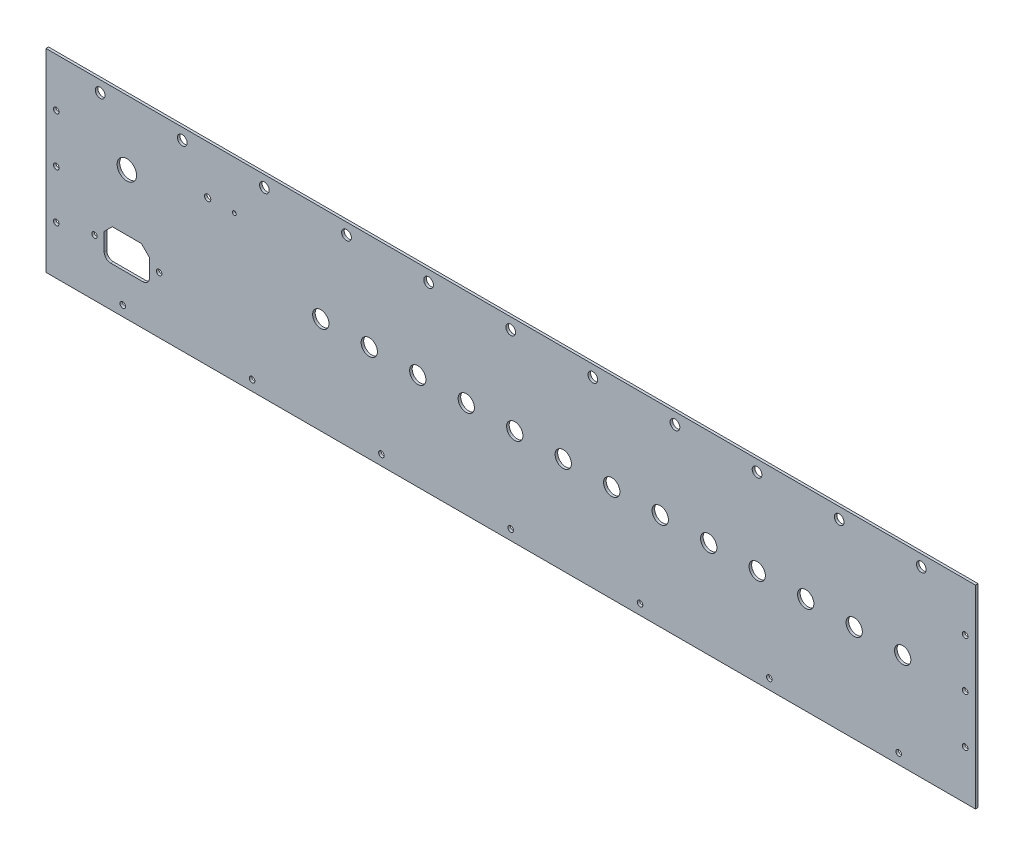
SolidWorks part; units mm, degrees
ref_plane "Front Plane" through (0, 0, 0) normal (0, 0, 1) x (1, 0, 0)
ref_plane "Top Plane" through (0, 0, 0) normal (0, 1, 0) x (1, 0, 0)
ref_plane "Right Plane" through (0, 0, 0) normal (1, 0, 0) x (0, 0, -1)
sketch "Sketch1" plane through (0, 0, 0) normal (0, 0, 1) x (1, 0, 0)
  line L1 (287.5, -60) -> (-287.5, -60)
  line L2 (287.5, -60) -> (287.5, 60)
  line L3 (287.5, 60) -> (-287.5, 60)
  line L4 (-287.5, -60) -> (-287.5, 60)
  line L5 (287.5, -60) -> (-287.5, 60) construction
  line L6 (287.5, 60) -> (-287.5, -60) construction
  point P0 (0, 0)
  dimension "D1" = 120
  dimension "D2" = 575
extrude "Boss-Extrude1" add sketch "Sketch1" along normal blind 1.5875
hole_wizard "M3 Clearance Hole1" positions "Sketch2" profile "Sketch3" hole size "M3" standard "ANSI Metric" end condition through all
sketch "Sketch2" plane through (0, 0, 1.5875) normal (0, 0, 1) x (1, 0, 0)
  line L0 (-287.5, 60) -> (-287.5, -60) construction
  line L1 (287.5, 60) -> (-287.5, 60) construction
  point P0 (-257.5, -25)
  point P2 (-217.5, -25)
  dimension "D1" = 40
  dimension "D2" = 30
  dimension "D3" = 85
sketch "Sketch3" plane through (-257.5, -25, 1.5875) normal (1, 0, 0) x (0, -1, 0)
  line L0 (0, 0) -> (0, 1.5875)
  line L1 (0, 1.5875) -> (1.7, 1.5875)
  line L2 (1.7, 1.5875) -> (1.7, 0)
  line L5 (1.7, 0) -> (0, 0)
  line L11 (0, -6.35) -> (0, 107.95) construction
  dimension "Thru Hole Dia." = 3.4
  dimension "Thru Hole Depth" = 1.5875
hole_wizard "3/8 Clearance Hole1" positions "Sketch4" profile "Sketch5" hole size "3/8" standard "ANSI Inch" end condition through all
sketch "Sketch4" plane through (0, 0, 1.5875) normal (0, 0, 1) x (1, 0, 0)
  line L0 (-287.5, 60) -> (-287.5, -60) construction
  point P0 (-117.5, 0)
  dimension "D1" = 170
sketch "Sketch5" plane through (-117.5, 0, 1.5875) normal (1, 0, 0) x (0, -1, 0)
  line L0 (0, 0) -> (0, 1.5875)
  line L1 (0, 1.5875) -> (5.0419, 1.5875)
  line L2 (5.0419, 1.5875) -> (5.0419, 0)
  line L5 (5.0419, 0) -> (0, 0)
  line L11 (0, -6.35) -> (0, 107.95) construction
  dimension "Thru Hole Dia." = 10.0838
  dimension "Thru Hole Depth" = 1.5875
pattern_linear "LPattern1" count 13 spacing 30 along (1, 0, 0) of "3/8 Clearance Hole1"
sketch "Sketch8" plane through (0, 0, 1.5875) normal (0, 0, 1) x (1, 0, 0)
  line L0 (287.5, 60) -> (-287.5, 60) construction
  line L1 (-287.5, 60) -> (-287.5, -60) construction
  circle A0 centre (-187.5, 30) radius 1.95
  circle A1 centre (-170.99, 30) radius 1.2
  dimension "D1" = 16.51
  dimension "D2" = 30
  dimension "D3" = 100
extrude "Cut-Extrude1" cut sketch "Sketch8" against normal up to next
sketch "Sketch9" plane through (0, 0, 1.5875) normal (0, 0, 1) x (1, 0, 0)
  line L1 (-223.5, -35) -> (-251.5, -35)
  line L2 (-223.5, -35) -> (-223.5, -15)
  line L3 (-223.5, -15) -> (-251.5, -15)
  line L4 (-251.5, -35) -> (-251.5, -15)
  line L5 (-223.5, -35) -> (-251.5, -15) construction
  line L6 (-223.5, -15) -> (-251.5, -35) construction
  circle A0 centre (-217.5, -25) radius 1.7 construction
  circle A1 centre (-257.5, -25) radius 1.7 construction
  point P0 (-237.5, -25)
  dimension "D1" = 20
  dimension "D2" = 28
  dimension "D3" = 20
  dimension "D4" = 0
extrude "Cut-Extrude2" cut sketch "Sketch9" against normal up to next
fillet "Fillet1" radius 4 2 edges at (-223.5, -35, 0.7937) (-251.5, -35, 0.7937)
chamfer "Chamfer1" distance 5 angle 45 2 edges at (-223.5, -15, 0.7937) (-251.5, -15, 0.7937)
sketch "Sketch10" plane through (0, 0, 1.5875) normal (0, 0, 1) x (1, 0, 0)
  line L0 (-287.5, 60) -> (-287.5, -60) construction
  line L1 (287.5, 60) -> (-287.5, 60) construction
  circle A0 centre (-237.5, 20) radius 6
  dimension "D1" = 50
  dimension "D2" = 40
extrude "Cut-Extrude3" cut sketch "Sketch10" against normal up to next
sketch "Sketch11" plane through (0, 0, 0) normal (0, 0, -1) x (-1, 0, 0)
  line L0 (-287.5, 60) -> (287.5, 60) construction
  line L1 (-287.5, -60) -> (-287.5, 60) construction
  circle A0 centre (-254, 53) radius 3
  dimension "D1" = 7
  dimension "D2" = 33.5
extrude "Cut-Extrude4" cut sketch "Sketch11" against normal up to next
pattern_linear "LPattern2" count 11 spacing 50.8 along (-1, 0, 0) of "Cut-Extrude4"
hole_wizard "#5 Clearance Hole1" positions "Sketch12" profile "Sketch13" hole size "#5" standard "ANSI Inch" end condition through all
sketch "Sketch12" plane through (0, 0, 0) normal (0, 0, -1) x (-1, 0, 0)
  line L0 (-287.5, -60) -> (-287.5, 60) construction
  line L1 (-287.5, 60) -> (287.5, 60) construction
  point P0 (-281.15, 30)
  point P3 (-281.15, 0)
  point P5 (-281.15, -30)
  dimension "D1" = 6.35
  dimension "D2" = 30
  dimension "D3" = 30
  dimension "D4" = 30
sketch "Sketch13" plane through (281.15, 30, 0) normal (1, 0, 0) x (0, 1, 0)
  line L0 (0, 0) -> (0, 1.5875)
  line L1 (0, 1.5875) -> (1.7272, 1.5875)
  line L2 (1.7272, 1.5875) -> (1.7272, 0)
  line L5 (1.7272, 0) -> (0, 0)
  line L11 (0, -6.35) -> (0, 107.95) construction
  dimension "Thru Hole Dia." = 3.4544
  dimension "Thru Hole Depth" = 1.5875
hole_wizard "#5 Clearance Hole2" positions "Sketch14" profile "Sketch15" hole size "#5" standard "ANSI Inch" end condition through all
sketch "Sketch14" plane through (0, 0, 0) normal (0, 0, -1) x (-1, 0, 0)
  line L0 (287.5, 60) -> (287.5, -60) construction
  line L1 (-287.5, 60) -> (287.5, 60) construction
  point P0 (281.15, 30)
  point P2 (281.15, 0)
  point P4 (281.15, -30)
  dimension "D1" = 6.35
  dimension "D2" = 6.35
  dimension "D3" = 6.35
  dimension "D4" = 30
  dimension "D5" = 30
  dimension "D6" = 30
sketch "Sketch15" plane through (-281.15, 30, 0) normal (1, 0, 0) x (0, 1, 0)
  line L0 (0, 0) -> (0, 1.5875)
  line L1 (0, 1.5875) -> (1.7272, 1.5875)
  line L2 (1.7272, 1.5875) -> (1.7272, 0)
  line L5 (1.7272, 0) -> (0, 0)
  line L11 (0, -6.35) -> (0, 107.95) construction
  dimension "Thru Hole Dia." = 3.4544
  dimension "Thru Hole Depth" = 1.5875
hole_wizard "#5 Clearance Hole3" positions "Sketch16" profile "Sketch17" hole size "#5" standard "ANSI Inch" end condition through all
sketch "Sketch16" plane through (0, 0, 0) normal (0, 0, -1) x (-1, 0, 0)
  line L0 (287.5, -60) -> (-287.5, -60) construction
  line L1 (-287.5, -60) -> (-287.5, 60) construction
  point P0 (-240, -53.65)
  point P5 (-160, -53.65)
  point P7 (-80, -53.65)
  point P9 (0, -53.65)
  point P11 (80, -53.65)
  point P13 (160, -53.65)
  point P15 (240, -53.65)
  dimension "D1" = 6.35
  dimension "D2" = 80
  dimension "D3" = 80
  dimension "D4" = 80
  dimension "D5" = 80
  dimension "D6" = 80
  dimension "D7" = 80
  dimension "D8" = 47.5
sketch "Sketch17" plane through (240, -53.65, 0) normal (1, 0, 0) x (0, 1, 0)
  line L0 (0, 0) -> (0, 1.5875)
  line L1 (0, 1.5875) -> (1.7272, 1.5875)
  line L2 (1.7272, 1.5875) -> (1.7272, 0)
  line L5 (1.7272, 0) -> (0, 0)
  line L11 (0, -6.35) -> (0, 107.95) construction
  dimension "Thru Hole Dia." = 3.4544
  dimension "Thru Hole Depth" = 1.5875
